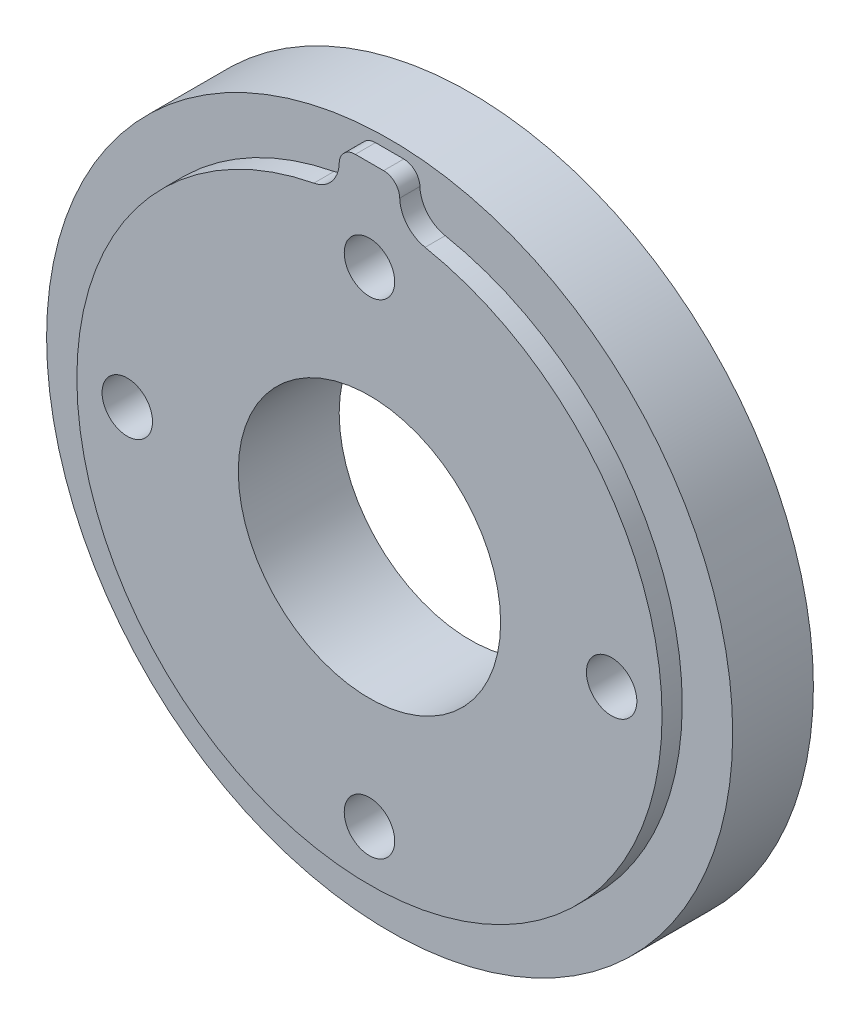
SolidWorks part; units mm, degrees
ref_plane "正面" through (0, 0, 0) normal (0, 0, 1) x (1, 0, 0)
ref_plane "平面" through (0, 0, 0) normal (0, 1, 0) x (1, 0, 0)
ref_plane "右側面" through (0, 0, 0) normal (1, 0, 0) x (0, 0, -1)
sketch "ｽｹｯﾁ1" plane through (0, 0, 0) normal (0, 0, 1) x (1, 0, 0)
  circle A0 centre (0, 0) radius 17
  dimension "D1" = 34
extrude "ﾎﾞｽ - 押し出し1" add sketch "ｽｹｯﾁ1" along normal blind 4
sketch "ｽｹｯﾁ2" plane through (0, 0, 4) normal (0, 0, 1) x (1, 0, 0)
  line L1 (-1.5, 12.5) -> (1.5, 12.5)
  line L2 (-1.5, 12.5) -> (-1.5, 16.5)
  line L3 (-1.5, 16.5) -> (1.5, 16.5)
  line L4 (1.5, 12.5) -> (1.5, 16.5)
  line L5 (-1.5, 12.5) -> (1.5, 16.5) construction
  line L6 (-1.5, 16.5) -> (1.5, 12.5) construction
  circle A0 centre (0, 0) radius 14.5
  point P3 (0, 14.5)
  circle M5 centre (0, 0) radius 17
  dimension "D1" = 29
  dimension "D2" = 2
  dimension "D3" = 3
extrude "ﾎﾞｽ - 押し出し2" add sketch "ｽｹｯﾁ2" along normal blind 1 contours A0 L4 L2 M5 | L4 L3 L2 M5 | L2 A0 L4 L1 | L4 A0 L2 L1 region at (0, 13.4872, 4) region at (0, -0.122, 4) region at (0, 15.4869, 4)
fillet "ﾌｨﾚｯﾄ1" radius 1.55 2 edges at (-1.5, 14.4222, 4.5) (1.5, 14.4222, 4.5)
fillet "ﾌｨﾚｯﾄ2" radius 0.8 2 edges at (1.5, 16.5, 4.5) (-1.5, 16.5, 4.5)
sketch "ｽｹｯﾁ3" plane through (0, 0, 5) normal (0, 0, 1) x (1, 0, 0)
  circle A0 centre (0, 0) radius 6.5
  dimension "D1" = 13
extrude "ｶｯﾄ - 押し出し1" cut sketch "ｽｹｯﾁ3" against normal through all
sketch "ｽｹｯﾁ4" plane through (0, 0, 0) normal (0, 0, -1) x (-1, 0, 0)
  circle A0 centre (0, 0) radius 12 construction
  circle A1 centre (0, 12) radius 1.25
  circle A2 centre (12, 0) radius 1.25
  circle A3 centre (0, -12) radius 1.25
  circle A4 centre (-12, 0) radius 1.25
  point P14 (0, 0)
  dimension "D1" = 24
  dimension "D2" = 2.5
  dimension "D3" = 4
extrude "ｶｯﾄ - 押し出し2" cut sketch "ｽｹｯﾁ4" against normal through all
